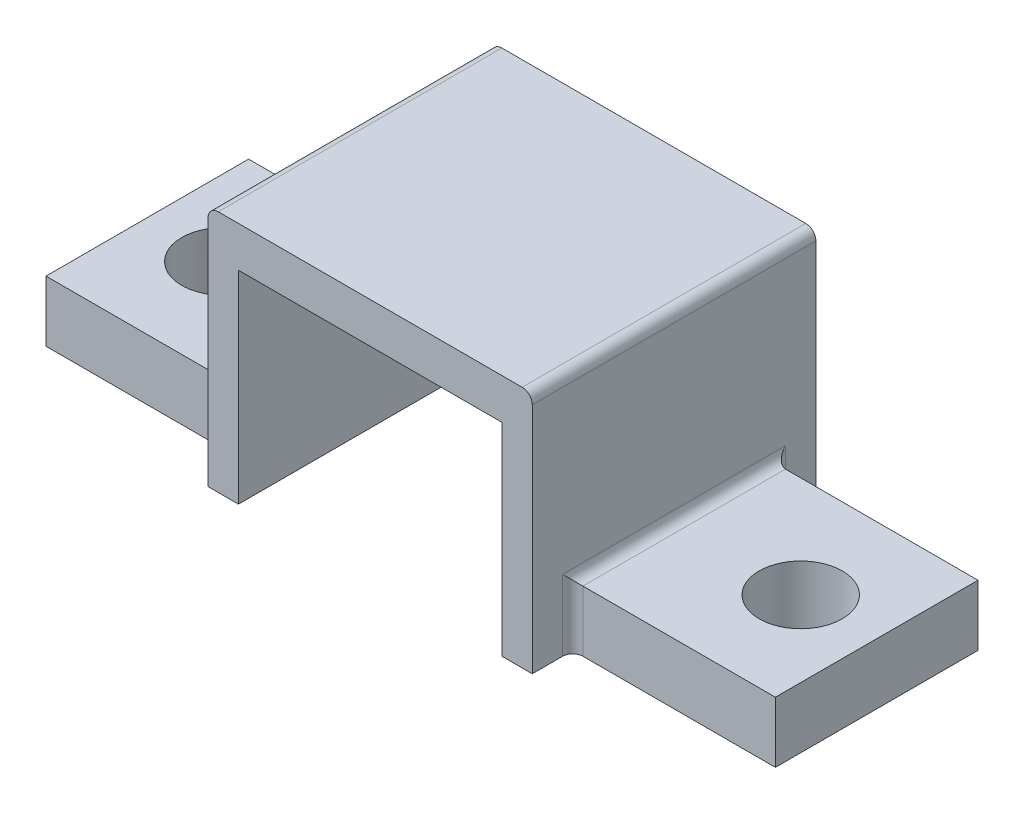
SolidWorks part; units mm, degrees
material "PLA"
ref_plane "Front Plane" through (0, 0, 0) normal (0, 0, 1) x (1, 0, 0)
ref_plane "Top Plane" through (0, 0, 0) normal (0, 1, 0) x (1, 0, 0)
ref_plane "Right Plane" through (0, 0, 0) normal (1, 0, 0) x (0, 0, -1)
sketch "Sketch1" plane through (0, 0, 0) normal (0, 0, 1) x (1, 0, 0)
  line L1 (-8, -6) -> (8, -6)
  line L2 (-8, -6) -> (-8, 6)
  line L3 (-8, 6) -> (8, 6)
  line L4 (8, -6) -> (8, 6)
  line L5 (-8, -6) -> (8, 6) construction
  line L6 (-8, 6) -> (8, -6) construction
  point P0 (0, 0)
  dimension "D1" = 16
  dimension "D2" = 12
extrude "Boss-Extrude1" add sketch "Sketch1" along normal mid plane 14
sketch "Sketch2" plane through (0, 0, 7) normal (0, 0, 1) x (1, 0, 0)
  line L0 (-8, -6) -> (8, -6) construction
  line L1 (-6.5, 4) -> (6.5, 4)
  line L2 (-6.5, 4) -> (-6.5, -6)
  line L3 (-6.5, -6) -> (6.5, -6)
  line L4 (6.5, 4) -> (6.5, -6)
  line L5 (-6.5, 4) -> (6.5, -6) construction
  line L6 (-6.5, -6) -> (6.5, 4) construction
  point P0 (0, -1)
  point P4 (0, 0)
  dimension "D1" = 13
  dimension "D2" = 10
extrude "Cut-Extrude1" cut sketch "Sketch2" against normal through all
sketch "Sketch6" plane through (0, -6, 0) normal (0, -1, 0) x (1, 0, 0)
  line L0 (-8, 7) -> (-8, -7) construction
  line L1 (-8, 7) -> (-8, -7)
  line L2 (0, -6.6) -> (0, 6.6) construction
  line L3 (-18, -5) -> (-8, -5)
  line L8 (-18, -5) -> (-18, 5)
  line L9 (-18, 5) -> (-8, 5)
  line L10 (-8, -5) -> (-8, 5)
  line L11 (18, 5) -> (8, 5)
  line L12 (8, -5) -> (8, 5)
  line L13 (18, -5) -> (8, -5)
  line L14 (18, -5) -> (18, 5)
  point P6 (-18, 0)
  dimension "D1" = 10
  dimension "D2" = 10
extrude "Boss-Extrude2" add sketch "Sketch6" against normal blind 3 contours L9 L8 L3 L1 | L13 L14 L11 L12 region at (-13, -6, 0) region at (13, -6, 0)
fillet "Fillet1" radius 0.5 8 edges at (8, 6, 0) (-8, 6, 0) (-8, -3, 0) (8, -3, 0) (8, -4.5, 5) (8, -4.5, -5) (-8, -4.5, -5) (-8, -4.5, 5)
sketch "Sketch9" plane through (0, -3, 0) normal (0, 1, 0) x (1, 0, 0)
  line L0 (0, -6.6) -> (0, 6.6) construction
  circle A0 centre (-14.25, 0) radius 2.05
  circle A1 centre (14.25, 0) radius 2.05
  dimension "D1" = 4.1
  dimension "D2" = 4.1
extrude "Cut-Extrude2" cut sketch "Sketch9" against normal blind 10 and the other way through all
ref_axis "Axis1" through (-14.25, -3, 0) along (0, -1, 0)
ref_axis "Axis2" through (14.25, -3, 0) along (0, -1, 0)
